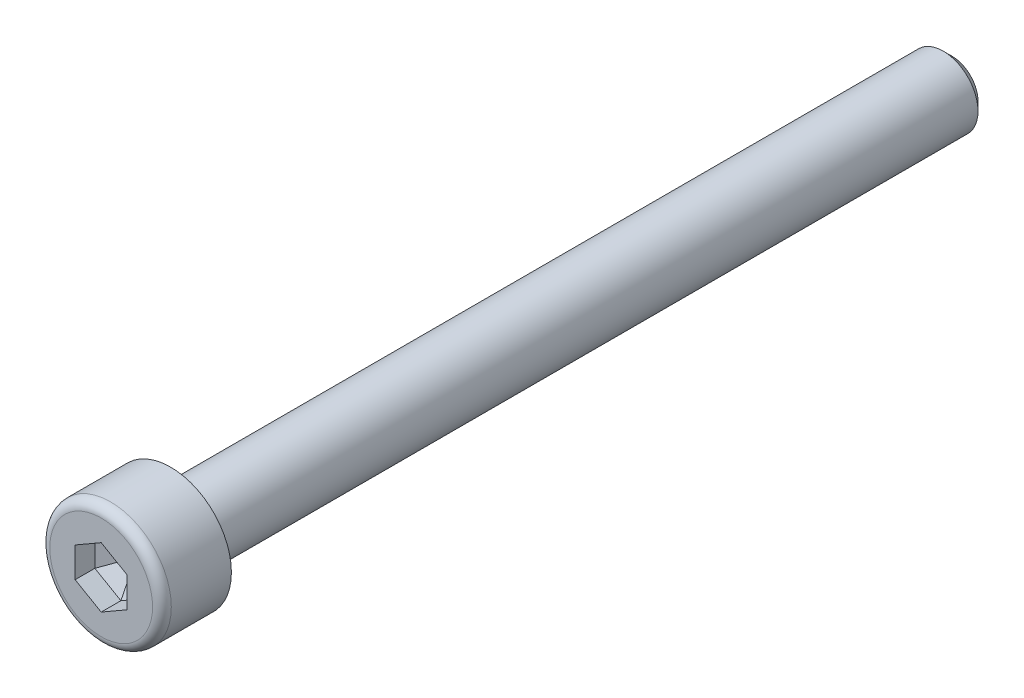
SolidWorks part; units mm, degrees
material "普通碳钢"
ref_plane "前视基准面" through (0, 0, 0) normal (0, 0, 1) x (1, 0, 0)
ref_plane "上视基准面" through (0, 0, 0) normal (0, 1, 0) x (1, 0, 0)
ref_plane "右视基准面" through (0, 0, 0) normal (1, 0, 0) x (0, 0, -1)
sketch "草图1" plane through (0, 0, 0) normal (0, 0, 1) x (1, 0, 0)
  circle A0 centre (0, 0) radius 3.5
  dimension "dk" = 7
extrude "凸台-拉伸1" add sketch "草图1" along normal blind 4
ref_axis "基准轴1" through (0, 0, 4) along (0, 0, -1)
sketch "草图2" plane through (0, 0, 4) normal (0, 0, 1) x (1, 0, 0)
  line L1 (1.5, 0.866) -> (0, 1.7321)
  line L2 (0, 1.7321) -> (-1.5, 0.866)
  line L3 (-1.5, 0.866) -> (-1.5, -0.866)
  line L4 (-1.5, -0.866) -> (0, -1.7321)
  line L5 (0, -1.7321) -> (1.5, -0.866)
  line L6 (1.5, -0.866) -> (1.5, 0.866)
  circle A0 centre (0, 0) radius 1.5 construction
  dimension "s" = 3
extrude "切除-拉伸1" cut sketch "草图2" against normal blind 2
sketch "草图3" plane through (0, 0, 0) normal (0, 0, -1) x (-1, 0, 0)
  circle A0 centre (0, 0) radius 2
  dimension "d" = 4
extrude "凸台-拉伸2" add sketch "草图3" along normal blind 45
cosmetic thread "装饰螺纹线1" parameters "b"=4.9, "D2"=1.221
chamfer "倒角1" distance 0.5 angle 45 1 edges at (-2, 0, -45)
fillet "圆角1" radius 0.5385 1 edges at (3.5, 0, 4)
chamfer "倒角2" distance 0.8646 angle 60 6 edges at (-1.5, 0, 2) (-0.75, 1.299, 2) (0.75, 1.299, 2) (1.5, 0, 2) (-0.75, -1.299, 2) (0.75, -1.299, 2) first distance on face at (-1.5, 0, 3) first distance on face at (-0.75, 1.299, 3) first distance on face at (0.75, 1.299, 3) first distance on face at (1.5, 0, 3) first distance on face at (-0.75, -1.299, 3) first distance on face at (0.75, -1.299, 3)
fillet "圆角2" radius 0.1 1 edges at (2, 0, 0)
ref_plane "基准面1" through (0, 0, 0) normal (0, 0, -1) x (-1, 0, 0)
equation "\"D1@倒角2\" = \"s@草图2\" / 3.47"
equation "\"D1@圆角1\"= \"dk@草图1\" / 13"
equation "\"D1@倒角1\"= \"d@草图3\" / 8"
equation "\"D1@圆角2\"= \"d@草图3\" / \"d@草图3\" * 0.1"
